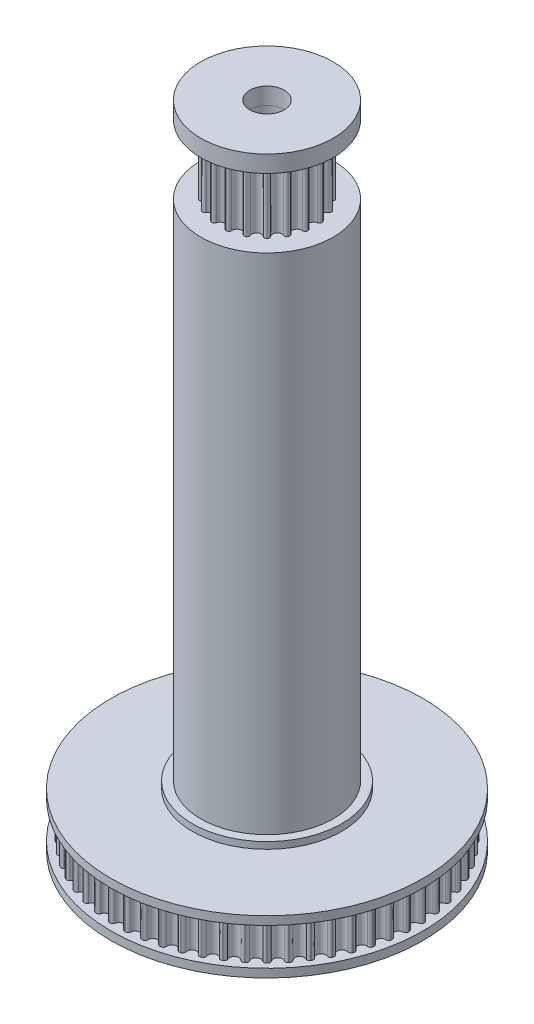
SolidWorks part; units mm, degrees
ref_plane "Front Plane" through (0, 0, 0) normal (0, 0, 1) x (1, 0, 0)
ref_plane "Top Plane" through (0, 0, 0) normal (0, 1, 0) x (1, 0, 0)
ref_plane "Right Plane" through (0, 0, 0) normal (1, 0, 0) x (0, 0, -1)
sketch "PulleyOffsets" plane through (0, 0, 0) normal (1, 0, 0) x (0, 0, -1)
  line L0 (53.975, 0) -> (-53.975, 0) construction
  line L1 (53.975, 107.95) -> (-53.975, 107.95) construction
  line L2 (0, 0) -> (0, 107.95) construction
  point P7 (0, 0)
  dimension "D1" = 107.95
ref_axis "Axis1" through (0, 34.9332, 0) along (0, -1, 0)
ref_plane "Big Pulley Plane" through (0, 0, 0) normal (0, 1, 0) x (1, 0, 0)
ref_plane "Small Pulley Plane" through (0, 107.95, 0) normal (0, 1, 0) x (1, 0, 0)
sketch "Sketch1" plane through (0, 0, 0) normal (0, 1, 0) x (1, 0, 0)
  line L0 (0, 0) -> (0, 28.2667) construction
  line L1 (0, 0) -> (2.9202, 27.7837) construction
  circle A0 centre (0, 0) radius 28.2667 construction
  circle A1 centre (0, 0) radius 27.0467 construction
  circle A2 centre (0, 27.9367) radius 0.89 construction
  circle A5 centre (2.9202, 27.7837) radius 0.89 construction
  arc A6 (0, 27.0467) -> (0.8804, 27.8061) centre (0, 27.9367) ccw
  arc A7 (0.8804, 27.8061) -> (1.3997, 28.2321) centre (1.3749, 27.7327) cw
  arc A8 (1.559, 28.2237) -> (2.031, 27.7458) centre (1.5314, 27.7245) cw
  arc A9 (2.8272, 26.8986) -> (2.031, 27.7458) centre (2.9202, 27.7837) cw
  arc A10 (1.3997, 28.2321) -> (1.559, 28.2237) centre (0, 0) cw
  arc A11 (0, 27.0467) -> (2.8272, 26.8986) centre (0, 0) ccw
  dimension "D1" = 56.5335
  dimension "D3" = 1.78
  dimension "D4" = 0.5
  dimension "D2" = 1.22
  dimension "D5" = 6
extrude "Boss-Extrude1" add sketch "Sketch1" along normal mid plane 7.112 contours A6 A11 A9 A8 A7 region at (0.001, 0, -0.0192)
pattern_circular "CirPattern1" count 60 over 360 about axis through (0, 34.9332, 0) along (0, -1, 0) of "Boss-Extrude1"
sketch "Sketch2" plane through (0, 0, 0) normal (1, 0, 0) x (0, 0, -1)
  line L10 (0, 3.5) -> (29.4415, 3.5) construction
  line L11 (0, 3.5) -> (0, 5.0875) construction
  line L12 (0, 5.0875) -> (29.4415, 5.0875) construction
  line L15 (29.4415, 3.5) -> (29.4415, 5.0875) construction
  line L20 (0, 34.9332) -> (0, -6.9932) construction
  line L22 (29.4415, 5.0875) -> (0, 5.0875)
  line L23 (29.4415, 5.0875) -> (29.4415, 3.5)
  line L24 (29.4415, 3.5) -> (0, 3.5)
  line L25 (0, 5.0875) -> (0, 3.5)
  dimension "D1" = 1.5875
  dimension "D2" = 29.4415
  dimension "D3" = 3.5
revolve "Revolve3" add sketch "Sketch2" angle 360 about axis through (0, 34.9332, 0) along (0, -1, 0) region at (0, 4.2937, -14.7207)
mirror "Mirror1" about plane through (0, 0, 0) normal (0, 1, 0) of "Revolve3"
sketch "Sketch3" plane through (0, 0, 0) normal (0, 1, 0) x (1, 0, 0)
  circle A0 centre (0, 0) radius 22.225
  dimension "D1" = 44.45
extrude "Cut-Extrude1" [suppressed] cut sketch "Sketch3" against normal through all both and the other way through all
sketch "Sketch6" plane through (0, 0, 0) normal (0, 1, 0) x (1, 0, 0)
  line L0 (0, 0) -> (0, 9.1676) construction
  line L1 (0, 0) -> (2.731, 8.405) construction
  circle A0 centre (0, 0) radius 9.1676 construction
  circle A1 centre (0, 0) radius 7.9476 construction
  circle A2 centre (0, 8.8376) radius 0.89 construction
  circle A5 centre (2.731, 8.405) radius 0.89 construction
  arc A6 (0, 7.9476) -> (0.8721, 8.6598) centre (0, 8.8376) ccw
  arc A7 (0.8721, 8.6598) -> (1.4405, 9.0537) centre (1.362, 8.5599) cw
  arc A8 (1.4277, 9.0557) -> (1.8466, 8.5054) centre (1.3498, 8.5618) cw
  arc A9 (2.4559, 7.5586) -> (1.8466, 8.5054) centre (2.731, 8.405) cw
  arc A10 (1.4405, 9.0537) -> (1.4277, 9.0557) centre (0, 0) cw construction
  arc A11 (0, 7.9476) -> (2.4559, 7.5586) centre (0, 0) ccw
  arc A12 (1.4405, 9.0537) -> (1.4277, 9.0557) centre (0, 0) cw
  dimension "D3" = 1.78
  dimension "D4" = 0.5
  dimension "D2" = 1.22
  dimension "D1" = 18.3352
  dimension "D5" = 18
extrude "Boss-Extrude2" add sketch "Sketch6" along normal mid plane 13 from surface contours A6 A11 A9 A8 A7 region at (0.0089, 0, -0.0564) starting at plane "Small Pulley Plane"
pattern_circular "CirPattern2" count 20 over 360 about axis through (0, 34.9332, 0) along (0, -1, 0) of "Boss-Extrude2"
sketch "Sketch4" plane through (0, 0, 0) normal (0, 0, 1) x (1, 0, 0)
  line L0 (14.0875, 5.0875) -> (-14.0875, 5.0875) construction
  line L1 (29.4415, 5.0875) -> (-29.4415, 5.0875) construction
  line L2 (-14.0875, 5.0875) -> (-14.0875, 6.3575)
  line L3 (-14.0875, 6.3575) -> (-12.5, 6.3575)
  line L4 (-12.5, 6.3575) -> (-12.5, 101.45)
  line L5 (0, 0) -> (0, 117.625) construction
  line L6 (12.5, 6.3575) -> (12.5, 101.45) construction
  line L7 (14.0875, 6.3575) -> (12.5, 6.3575) construction
  line L8 (14.0875, 5.0875) -> (14.0875, 6.3575) construction
  line L9 (-12.5, 101.45) -> (12.5, 101.45) construction
  line L10 (-14.0875, 5.0875) -> (0, 5.0875)
  line L11 (0, 5.0875) -> (0, 101.45)
  line L12 (0, 101.45) -> (-12.5, 101.45)
  line L13 (1.841, 101.45) -> (3.5054, 101.45) construction
  line L14 (0.8721, 114.45) -> (-0.8721, 114.45) construction
  line L15 (-12.5, 117.625) -> (0, 117.625)
  line L16 (-12.5, 117.625) -> (-12.5, 114.45)
  line L17 (-12.5, 114.45) -> (0, 114.45)
  line L18 (0, 117.625) -> (0, 114.45)
  line L19 (-12.5, 101.45) -> (-12.5, 114.45) construction
  point P14 (0, 5.0875)
  dimension "D1" = 1.27
  dimension "D2" = 1.5875
  dimension "D3" = 25
  dimension "D4" = 3.175
revolve "Revolve4" add sketch "Sketch4" angle 360 about L11
sketch "Sketch7" plane through (0, 117.625, 0) normal (0, 1, 0) x (1, 0, 0)
  circle A0 centre (0, 0) radius 3.2385
  dimension "D1" = 6.477
extrude "Cut-Extrude2" cut sketch "Sketch7" against normal through all both and the other way through all
equation "\"TEETH_NUM\"= 60"
equation "\"TOOTH_PITCH\"= 3mm"
equation "\"PITCH_LINE_OFFSET\"= .015in"
equation "\"DIAMETER_PER_GROOVE\"= \"OUTSIDE_DIAMETER\" / \"TEETH_NUM\" * 1in"
equation "\"PITCH_DIAMETER\"= ( ( \"TEETH_NUM\" * 3 - 1.31 ) / 3.1415 + .415 ) * 1mm"
equation "\"OUTSIDE_DIAMETER\"= \"PITCH_DIAMETER\" - \"PITCH_LINE_OFFSET\" * 2"
equation "\"D1@Sketch1\"=\"OUTSIDE_DIAMETER\""
equation "\"TOOTH_HEIGHT\"= 1.22mm"
equation "\"D2@Sketch1\"=\"TOOTH_HEIGHT\""
equation "\"TOOTH_DIAMETER\"= 1.78mm"
equation "\"INTERNAL_RADIUS\"= .5mm"
equation "\"D3@Sketch1\"=\"TOOTH_DIAMETER\""
equation "\"D5@Sketch1\"=360 / \"TEETH_NUM\""
equation "\"D4@Sketch1\"=\"INTERNAL_RADIUS\""
equation "\"D1@CirPattern1\"=\"TEETH_NUM\""
equation "\"BELT_GAP\"= 7mm"
equation "\"D2@Sketch2\"=\"PITCH_DIAMETER\"/2+1/32"
equation "\"D3@Sketch2\"=\"BELT_GAP\"/2"
equation "\"2_TEETH_NUM\"= 20"
equation "\"2_PITCH_DIAMETER\"= ( ( \"2_TEETH_NUM\" * 3 - 1.31 ) / 3.1415 + .415 ) * 1mm"
equation "\"2_OUTSIDE_DIAMETER\"= \"2_PITCH_DIAMETER\" - \"PITCH_LINE_OFFSET\" * 2"
equation "\"2_DIAMETER_PER_GROOVE\"= \"2_OUTSIDE_DIAMETER\" / \"2_TEETH_NUM\" * 1in"
equation "\"D5@Sketch6\"=360/\"2_TEETH_NUM\""
equation "\"D1@Sketch6\"=\"2_OUTSIDE_DIAMETER\""
equation "\"D2@Sketch6\"=\"TOOTH_HEIGHT\""
equation "\"D3@Sketch6\"=\"TOOTH_DIAMETER\""
equation "\"D4@Sketch6\"=\"INTERNAL_RADIUS\""
equation "\"2_BELT_GAP\"= 13mm"
equation "\"D1@CirPattern2\"=\"2_TEETH_NUM\""
equation "\"D1@Boss-Extrude2\"=\"2_BELT_GAP\""
equation "\"Pulley_OffSets\"= 4.25"
equation "\"D1@PulleyOffsets\" = \"Pulley_OffSets\""
